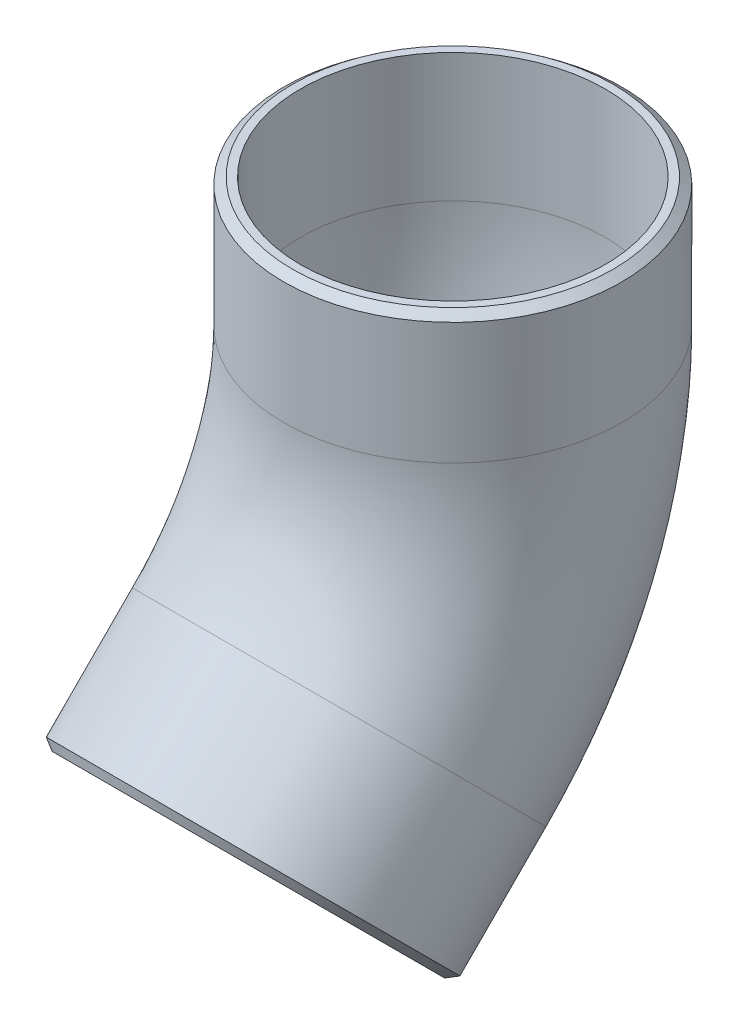
SolidWorks part; units mm, degrees
ref_plane "Front Plane" through (0, 0, 0) normal (0, 0, 1) x (1, 0, 0)
ref_plane "Top Plane" through (0, 0, 0) normal (0, 1, 0) x (1, 0, 0)
ref_plane "Right Plane" through (0, 0, 0) normal (1, 0, 0) x (0, 0, -1)
sketch "Sketch1" plane through (0, 0, 0) normal (1, 0, 0) x (0, 0, -1)
  line L0 (-20.2056, -20.2056) -> (-11.2253, -11.2253)
  line L1 (-11.2253, -11.2253) -> (0, 0) construction
  line L2 (0, 0) -> (0, 15.875) construction
  line L3 (0, 15.875) -> (0, 28.575)
  line L4 (-30.8472, -9.564) -> (-9.564, -30.8472) construction
  line L5 (-30.8472, -9.564) -> (-32.0146, -8.3965) construction
  line L6 (-9.564, -30.8472) -> (-8.3965, -32.0146) construction
  line L7 (-15.0495, 28.575) -> (15.0495, 28.575) construction
  line L8 (15.0495, 28.575) -> (16.7005, 28.575) construction
  line L9 (-15.0495, 28.575) -> (-16.7005, 28.575) construction
  line L12 (-11.2253, -11.2253) -> (-38.3256, 15.875) construction
  line L13 (-38.3256, 15.875) -> (0, 15.875) construction
  arc A0 (-11.2253, -11.2253) -> (0, 15.875) centre (-38.3256, 15.875) ccw
  dimension "D1" = 45
  dimension "A" = 28.575
  dimension "OD" = 33.401
  dimension "Tanget" = 12.7
  dimension "WT" = 1.651
ref_plane "Plane1" through (0, 28.575, 0) normal (0, 1, 0) x (1, 0, 0)
sketch "Sketch2" plane through (0, 28.575, 0) normal (0, 1, 0) x (1, 0, 0)
  circle A0 centre (0, 0) radius 15.0495
  circle A1 centre (0, 0) radius 16.7005
sweep "Sweep1" add profiles "Sketch2" path "Sketch1"
sketch "Sketch3" plane through (0, 0, 0) normal (-1, 0, 0) x (0, 1, 0)
  line L3 (28.575, 0) -> (15.875, 0) construction
  line L5 (28.575, -15.0495) -> (28.575, 15.0495) construction
  line L6 (15.875, -16.7005) -> (15.875, 16.7005) construction
  line L8 (15.875, 0) -> (-11.2253, -11.2253) construction
  line L10 (-11.2253, -11.2253) -> (-20.2056, -20.2056) construction
  line L12 (-32.0146, -8.3965) -> (-8.3965, -32.0146) construction
  line L19 (0.5837, -23.0344) -> (-23.0344, 0.5837) construction
  line L20 (-31.4084, -9.0027) -> (-32.0146, -8.3965)
  line L21 (-32.0146, -8.3965) -> (-31.5495, -7.9314)
  line L22 (-23.0344, 0.5837) -> (-32.0146, -8.3965) construction
  line L23 (-31.5495, -7.9314) -> (-31.4084, -9.0027)
  line L25 (28.575, 15.8432) -> (27.9172, 16.7005)
  line L26 (28.575, -16.7005) -> (28.575, 16.7005) construction
  line L27 (28.575, 16.7005) -> (15.875, 16.7005) construction
  line L28 (27.9172, 16.7005) -> (28.575, 16.7005)
  line L29 (28.575, 16.7005) -> (28.575, 15.8432)
  point P27 (28.575, 15.0495)
  dimension "D1" = 0.7937
  dimension "D2" = 37.5
revolve "Cut-Revolve1" cut sketch "Sketch3" angle 360 about L3 region at (0, 28.3557, -16.4147)
revolve "Cut-Revolve2" cut sketch "Sketch3<7>" angle 360 about L10
sketch "Sketch3<7>" plane through (0, 0, 0) normal (-1, 0, 0) x (0, 1, 0) same geometry as "Sketch3"
scale "Scale1" scale about centroid uniform scaling yes scale factor 0.095238
